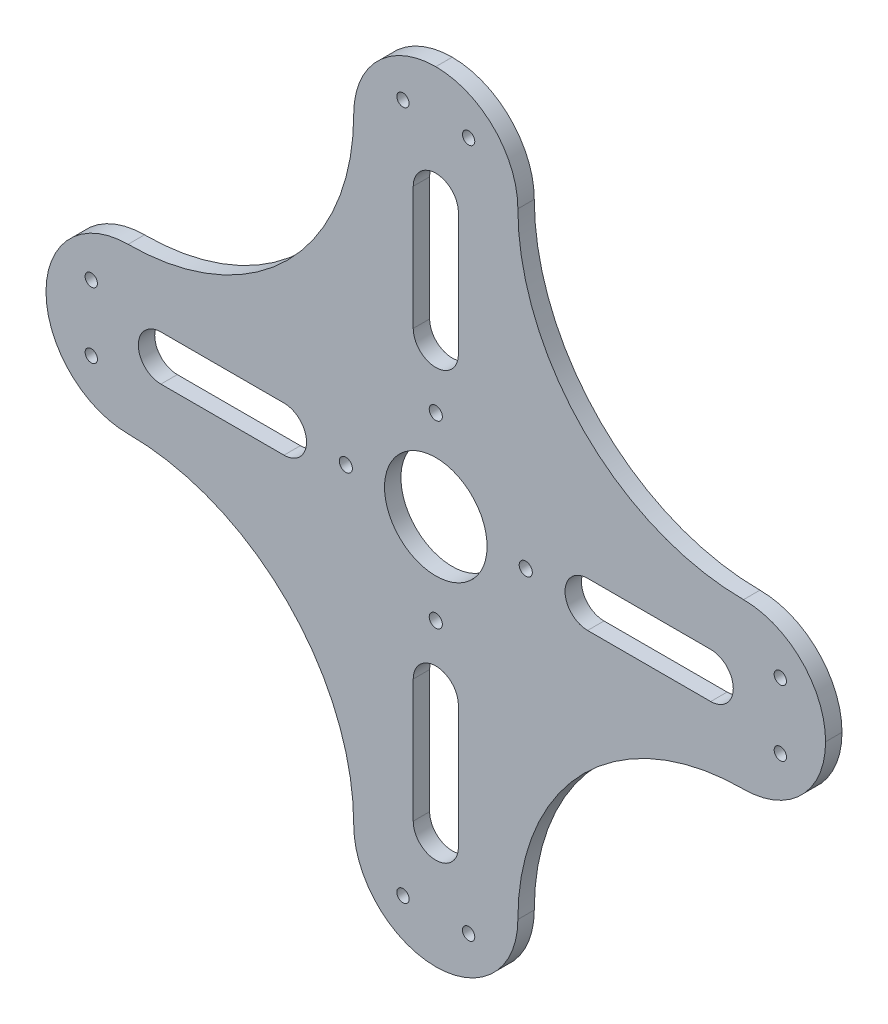
SolidWorks part; units mm, degrees
ref_plane "Front Plane" through (0, 0, 0) normal (0, 0, 1) x (1, 0, 0)
ref_plane "Top Plane" through (0, 0, 0) normal (0, 1, 0) x (1, 0, 0)
ref_plane "Right Plane" through (0, 0, 0) normal (1, 0, 0) x (0, 0, -1)
sketch "Sketch1" plane through (0, 0, 0) normal (0, 0, 1) x (1, 0, 0)
  line L13 (-95, -95) -> (95, -95)
  line L14 (-95, -95) -> (-95, 95)
  line L15 (-95, 95) -> (95, 95)
  line L16 (95, -95) -> (95, 95)
  line L17 (-95, -95) -> (95, 95) construction
  line L18 (-95, 95) -> (95, -95) construction
  line L19 (-75, -75) -> (75, -75)
  line L20 (-75, -75) -> (-75, 75)
  line L21 (-75, 75) -> (75, 75)
  line L22 (75, -75) -> (75, 75)
  line L23 (-75, -75) -> (75, 75) construction
  line L24 (-75, 75) -> (75, -75) construction
  line L39 (-75, -24.9122) -> (-75, 26.5574)
  line L48 (-95, -20.0021) -> (-75, -20.0021)
  line L49 (-75, -20.0021) -> (-75, 20.0021)
  line L50 (-75, 20.0021) -> (-95, 20.0021)
  line L51 (-95, 20.0021) -> (-95, -20.0021)
  line L64 (-72, -72) -> (-72, 72)
  line L65 (-72, 72) -> (72, 72)
  line L70 (72, -72) -> (72, 72)
  line L71 (-72, -72) -> (72, -72)
  line L72 (-10.5, -75) -> (10.5, -75)
  line L77 (75, -10.5) -> (64, -10.5)
  line L78 (75, -10.5) -> (75, 10.5)
  line L79 (75, 10.5) -> (64, 10.5)
  line L80 (64, -10.5) -> (64, 10.5)
  line L81 (-10.5, -75) -> (-10.5, -64)
  line L82 (-10.5, -64) -> (10.5, -64)
  line L83 (10.5, -75) -> (10.5, -64)
  line L84 (-75, 10.5) -> (-75, -10.5)
  line L85 (-75, 10.5) -> (-64, 10.5)
  line L86 (-64, 10.5) -> (-64, -10.5)
  line L87 (-75, -10.5) -> (-64, -10.5)
  line L88 (10.5, 75) -> (-10.5, 75)
  line L89 (10.5, 75) -> (10.5, 64)
  line L90 (10.5, 64) -> (-10.5, 64)
  line L91 (-10.5, 75) -> (-10.5, 64)
  line L92 (-75, 45) -> (-72, 45)
  line L93 (-45, 75) -> (-45, 72)
  line L94 (-20.0021, 95) -> (-20.0021, 75)
  line L95 (-20.0021, 75) -> (20.0021, 75)
  line L96 (20.0021, 75) -> (20.0021, 95)
  line L97 (20.0021, 95) -> (-20.0021, 95)
  line L98 (95, 20.0021) -> (75, 20.0021)
  line L99 (75, 20.0021) -> (75, -20.0021)
  line L100 (75, -20.0021) -> (95, -20.0021)
  line L101 (95, -20.0021) -> (95, 20.0021)
  line L102 (20.0021, -95) -> (20.0021, -75)
  line L103 (20.0021, -75) -> (-20.0021, -75)
  line L104 (-20.0021, -75) -> (-20.0021, -95)
  line L105 (-20.0021, -95) -> (20.0021, -95)
  line L106 (-85, 20.0021) -> (-85, -20.0021) construction
  circle A12 centre (-83.9698, 8) radius 1.5
  circle A13 centre (-83.9698, -8) radius 1.5
  circle A15 centre (8, 83.9698) radius 1.5
  circle A17 centre (-8, 83.9698) radius 1.5
  circle A18 centre (83.9698, -8) radius 1.5
  circle A20 centre (83.9698, 8) radius 1.5
  circle A21 centre (-8, -83.9698) radius 1.5
  circle A23 centre (8, -83.9698) radius 1.5
  arc A24 (-75, 20.0021) -> (-20.0021, 75) centre (-75, 75) ccw
  arc A25 (20.0021, 75) -> (75, 20.0021) centre (75, 75) ccw
  arc A26 (75, -20.0021) -> (20.0021, -75) centre (75, -75) ccw
  arc A27 (-20.0021, -75) -> (-75, -20.0021) centre (-75, -75) ccw
  point P0 (0, 0)
  point P5 (-85, 0)
  point P6 (-64, 0)
  point P11 (0, 0)
  point P85 (0, 0)
  point P95 (0, 0)
  dimension "D3" = 3
  dimension "D1" = 190
  dimension "D2" = 190
  dimension "D4" = 150
  dimension "D5" = 4
  dimension "D6" = 4
  dimension "D8" = 11
  dimension "D7" = 21
  dimension "D10" = 45
  dimension "D11" = 45
  dimension "D9" = 4
extrude "Boss-Extrude1" add sketch "Sketch1" along normal blind 4 contours A24 L39 L85 L64 | L49 L87 L64 L85 | L49 L39 L50 L14 L48 A13 A12 | L64 L87 L86 L85 | A27 L64 L87 L39 | A27 L71 L81 L82 L83 A26 L70 L77 L80 L79 A25 L65 L89 L90 L91 A24 L64 L85 L86 L87 | L65 L91 L90 L89 | L21 L96 L15 L94 A17 A15 | A25 L21 L89 L65 | L21 L91 L65 L89 | A24 L65 L91 L21 | L80 L77 L70 L79 | L22 L79 L70 L77 | A26 L22 L77 L70 | A25 L70 L79 L22 | L22 L100 L16 L98 A20 A18 | A26 L71 L83 L19 | L19 L83 L71 L81 | L71 L83 L82 L81 | A27 L19 L81 L71 | L19 L104 L13 L102 A23 A21 region at (0, -85.0185, 0) region at (-85.0185, 0, 0) region at (-15.2647, -73.4979, 0) region at (-73.4979, -15.2647, 0) region at (15.2647, -73.4979, 0) region at (0, -73.5, 0) region at (0, 0, 0) region at (-73.4979, 15.2647, 0) region at (-73.5, 0, 0) region at (85.0185, 0, 0) region at (0, -68, 0) region at (0, 85.0185, 0) region at (-68, 0, 0) region at (73.4979, -15.2647, 0) region at (-15.2647, 73.4979, 0) region at (73.4979, 15.2647, 0) region at (73.5, 0, 0) region at (68, 0, 0) region at (15.2647, 73.4979, 0) region at (0, 73.5, 0) region at (0, 68, 0)
sketch "Sketch6" plane through (0, 0, 0) normal (0, 0, 1) x (1, 0, 0)
  line L7 (0, 37) -> (0, 67) construction
  line L16 (-5.5, 37) -> (-5.5, 67)
  line L18 (5.5, 37) -> (5.5, 67)
  line L29 (37, -5.5) -> (67, -5.5)
  line L30 (37, 5.5) -> (67, 5.5)
  line L35 (37, 0) -> (67, 0) construction
  line L36 (-5.5, -37) -> (-5.5, -67)
  line L37 (5.5, -37) -> (5.5, -67)
  line L40 (0, -37) -> (0, -67) construction
  line L43 (-37, 5.5) -> (-67, 5.5)
  line L46 (-37, -5.5) -> (-67, -5.5)
  line L51 (-37, 0) -> (-67, 0) construction
  arc A3 (-5.5, 37) -> (5.5, 37) centre (0, 37) ccw
  arc A12 (75, 20.9897) -> (20.9897, 75) centre (93.8629, 93.8629) cw
  arc A13 (5.5, 67) -> (-5.5, 67) centre (0, 67) ccw
  circle A14 centre (0, 0) radius 12.5
  arc A15 (37, 5.5) -> (37, -5.5) centre (37, 0) ccw
  arc A16 (67, -5.5) -> (67, 5.5) centre (67, 0) ccw
  arc A17 (5.5, -37) -> (-5.5, -37) centre (0, -37) ccw
  arc A18 (-5.5, -67) -> (5.5, -67) centre (0, -67) ccw
  arc A19 (-37, -5.5) -> (-37, 5.5) centre (-37, 0) ccw
  arc A20 (-67, 5.5) -> (-67, -5.5) centre (-67, 0) ccw
  point P2 (0, 52)
  point P13 (52, 0)
  point P23 (0, -52)
  point P31 (-52, 0)
  point P69 (-50, 0)
  dimension "D1" = 52
  dimension "D2" = 25
  dimension "D3" = 11
  dimension "D4" = 30
extrude "Cut-Extrude15" cut sketch "Sketch6" against normal mid plane 10 contours A12 | L43 A20 L46 A19 | A14 | L30 A16 L29 A15 | A3 L18 A13 L16 | A17 L36 A18 L37
sketch "Sketch11" plane through (0, 0, 0) normal (0, 0, 1) x (1, 0, 0)
  line L0 (-95, 20.0021) -> (-135.0042, 20.0021)
  line L1 (-95, 20.0021) -> (-75, 20.0021)
  line L2 (-95, 20.0021) -> (-95, -20.0021)
  line L3 (-95, -20.0021) -> (-75, -20.0021)
  line L4 (-75, 20.0021) -> (-75, -20.0021)
  line L5 (-95, 20.0021) -> (-95, 0.0021)
  line L6 (-95, 0.0021) -> (-135.0042, 0.0021)
  line L7 (-135.0042, 20.0021) -> (-135.0042, 0.0021)
  line L8 (-95, 20.0021) -> (-95, 60.0063)
  line L9 (-95, 20.0021) -> (-115, 20.0021)
  line L10 (-115, 20.0021) -> (-115, 60.0063)
  line L11 (-95, 60.0063) -> (-115, 60.0063)
  line L12 (-95, 20.0021) -> (-54.9958, 20.0021)
  line L13 (-95, 20.0021) -> (-95, 40.0021)
  line L14 (-95, 40.0021) -> (-54.9958, 40.0021)
  line L15 (-54.9958, 20.0021) -> (-54.9958, 40.0021)
  circle A0 centre (-83.9698, 8) radius 1.5
  circle A1 centre (-83.9698, -8) radius 1.5
  circle A2 centre (-107.0021, 8.9719) radius 1.5
  circle A3 centre (-123.0021, 8.9719) radius 1.5
  circle A4 centre (-106.0302, 32.0042) radius 1.5
  circle A5 centre (-106.0302, 48.0042) radius 1.5
  circle A6 centre (-82.9979, 31.0323) radius 1.5
  circle A7 centre (-66.9979, 31.0323) radius 1.5
  dimension "D1" = 3
extrude "Boss-Extrude2" add sketch "Sketch11" along normal blind 6 from surface rebuild error yes starting at face at (-52, 0, 4)
fillet "Fillet5" radius 20 8 edges at (95, -20.0021, 2) (95, 20.0021, 2) (20.0021, 95, 2) (-20.0021, 95, 2) (-95, -20.0021, 2) (-95, 20.0021, 2) (-20.0021, -95, 2) (20.0021, -95, 2)
fillet "Fillet6" radius 20 rebuild error yes
sketch "Sketch10" plane through (0, 0, 0) normal (0, 0, 1) x (1, 0, 0)
  line L0 (0, 21.9203) -> (-21.9203, 0) construction
  line L5 (0, 21.9203) -> (21.9203, 0) construction
  line L7 (-21.9203, 0) -> (0, -21.9203) construction
  line L8 (21.9203, 0) -> (0, -21.9203) construction
  circle A8 centre (0, 21.9203) radius 1.6
  circle A9 centre (21.9203, 0) radius 1.6
  circle A10 centre (0, -21.9203) radius 1.6
  circle A11 centre (-21.9203, 0) radius 1.6
  dimension "D1" = 31
  dimension "D2" = 31
  dimension "D3" = 3.2
extrude "Cut-Extrude16" cut sketch "Sketch10" along normal through all both and the other way through all contours A10 | A9 | A8 | A11 region at (0, 21.9203, 0) region at (21.9203, 0, 0) region at (0, -21.9203, 0) region at (-21.9203, 0, 0)
